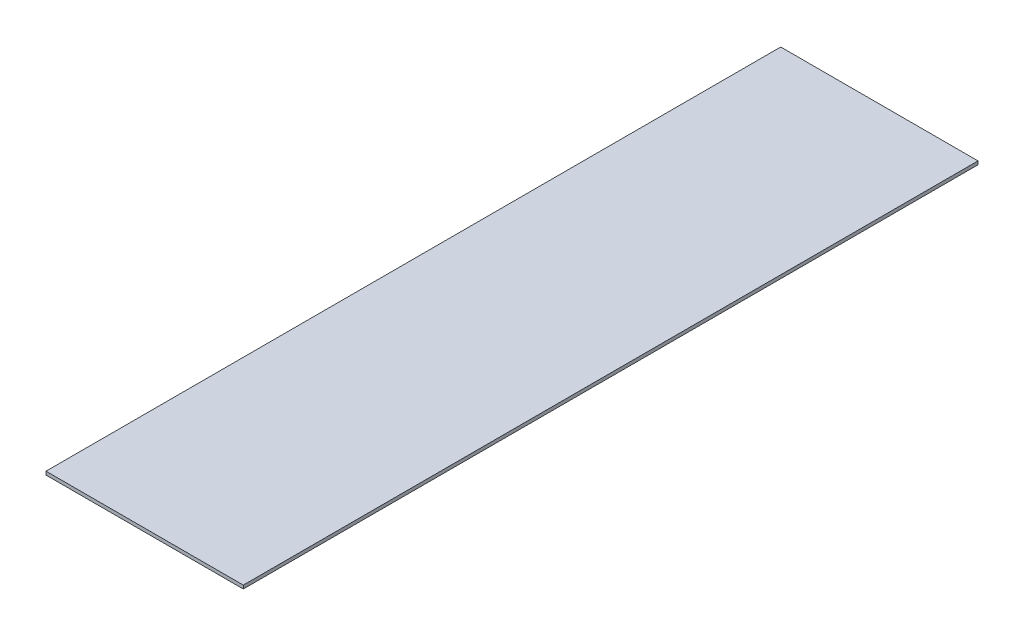
SolidWorks part; units mm, degrees
ref_plane "Front Plane" through (0, 0, 0) normal (0, 0, 1) x (1, 0, 0)
ref_plane "Top Plane" through (0, 0, 0) normal (0, 1, 0) x (1, 0, 0)
ref_plane "Right Plane" through (0, 0, 0) normal (1, 0, 0) x (0, 0, -1)
sketch "Sketch1" plane through (0, 0, 0) normal (0, 1, 0) x (1, 0, 0)
  line L1 (0, 0) -> (184.15, 0)
  line L2 (0, 0) -> (0, 685.8)
  line L3 (0, 685.8) -> (184.15, 685.8)
  line L4 (184.15, 0) -> (184.15, 685.8)
  dimension "D1" = 685.8
  dimension "D2" = 184.15
extrude "Boss-Extrude1" add sketch "Sketch1" along normal blind 3.175
